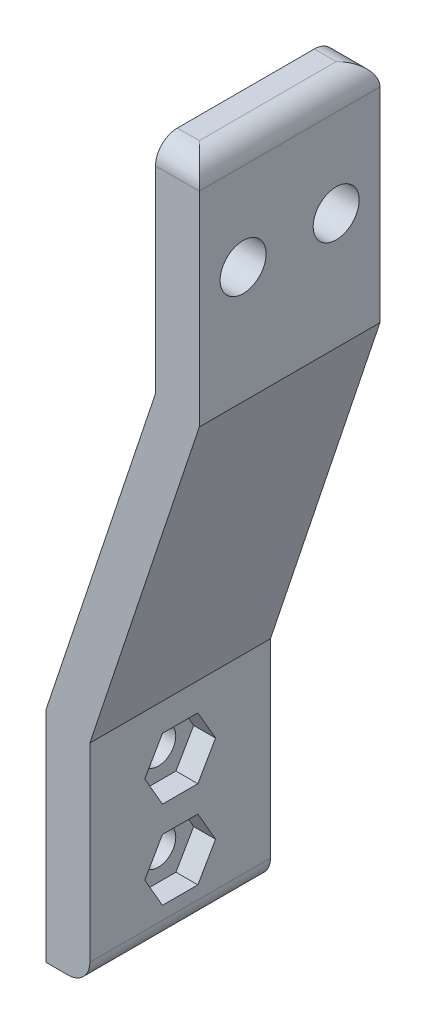
SolidWorks part; units mm, degrees
ref_plane "Front Plane" through (0, 0, 0) normal (0, 0, 1) x (1, 0, 0)
ref_plane "Top Plane" through (0, 0, 0) normal (0, 1, 0) x (1, 0, 0)
ref_plane "Right Plane" through (0, 0, 0) normal (1, 0, 0) x (0, 0, -1)
sketch "Sketch3" plane through (0, 0, 0) normal (0, 0, 1) x (1, 0, 0)
  line L0 (0, 0) -> (0, 20)
  line L1 (0, 20) -> (10, 50)
  line L2 (10, 50) -> (10, 70)
  line L3 (10, 70) -> (14, 70)
  line L4 (14, 70) -> (14, 49.3509)
  line L5 (14, 49.3509) -> (4, 19.3509)
  line L6 (4, 19.3509) -> (4, 0)
  line L7 (4, 0) -> (0, 0)
  dimension "D1" = 4
  dimension "D2" = 4
  dimension "D3" = 10
  dimension "D4" = 70
  dimension "D5" = 20
  dimension "D6" = 20
  dimension "D7" = 4
extrude "Boss-Extrude2" add sketch "Sketch3" along normal blind 16.5
sketch "Sketch4" plane through (14, 0, 0) normal (1, 0, 0) x (0, 0, -1)
  line L0 (-16.5, 70) -> (0, 70) construction
  line L1 (-16.5, 49.3509) -> (-16.5, 70) construction
  line L2 (0, 49.3509) -> (0, 70) construction
  circle A0 centre (-12.5, 60) radius 2.1
  circle A1 centre (-4, 60) radius 2.1
  dimension "D1" = 4.2
  dimension "D2" = 10
  dimension "D3" = 4
  dimension "D4" = 4
extrude "Cut-Extrude2" cut sketch "Sketch4" against normal blind 16.5
sketch "Sketch5" plane through (4, 0, 0) normal (1, 0, 0) x (0, 0, -1)
  line L0 (-16.5, 0) -> (0, 0) construction
  line L1 (-16.5, 0) -> (-16.5, 19.3509) construction
  circle A0 centre (-8.25, 14) radius 1.6
  circle A1 centre (-8.25, 6) radius 1.6
  dimension "D1" = 3.2
  dimension "D2" = 8
  dimension "D3" = 6
  dimension "D4" = 8.25
extrude "Cut-Extrude3" cut sketch "Sketch5" against normal up to next
fillet "Fillet1" radius 2 2 edges at (14, 70, 8.25) (4, 0, 8.25)
fillet "Fillet2" radius 2 2 edges at (11, 70, 0) (11, 70, 16.5) tangent propagation no
sketch "Sketch6" plane through (4, 0, 0) normal (1, 0, 0) x (0, 0, -1)
  line L1 (-5.0168, 14) -> (-6.6334, 16.8)
  line L2 (-6.6334, 16.8) -> (-9.8666, 16.8)
  line L3 (-9.8666, 16.8) -> (-11.4832, 14)
  line L4 (-11.4832, 14) -> (-9.8666, 11.2)
  line L5 (-9.8666, 11.2) -> (-6.6334, 11.2)
  line L6 (-6.6334, 11.2) -> (-5.0168, 14)
  line L7 (-6.6334, 8.8) -> (-9.8666, 8.8)
  line L8 (-9.8666, 8.8) -> (-11.4832, 6)
  line L9 (-11.4832, 6) -> (-9.8666, 3.2)
  line L10 (-9.8666, 3.2) -> (-6.6334, 3.2)
  line L11 (-6.6334, 3.2) -> (-5.0168, 6)
  line L12 (-5.0168, 6) -> (-6.6334, 8.8)
  circle A0 centre (-8.25, 14) radius 2.8 construction
  circle A1 centre (-8.25, 6) radius 2.8 construction
  dimension "D1" = 5.6
extrude "Cut-Extrude4" cut sketch "Sketch6" against normal blind 2
